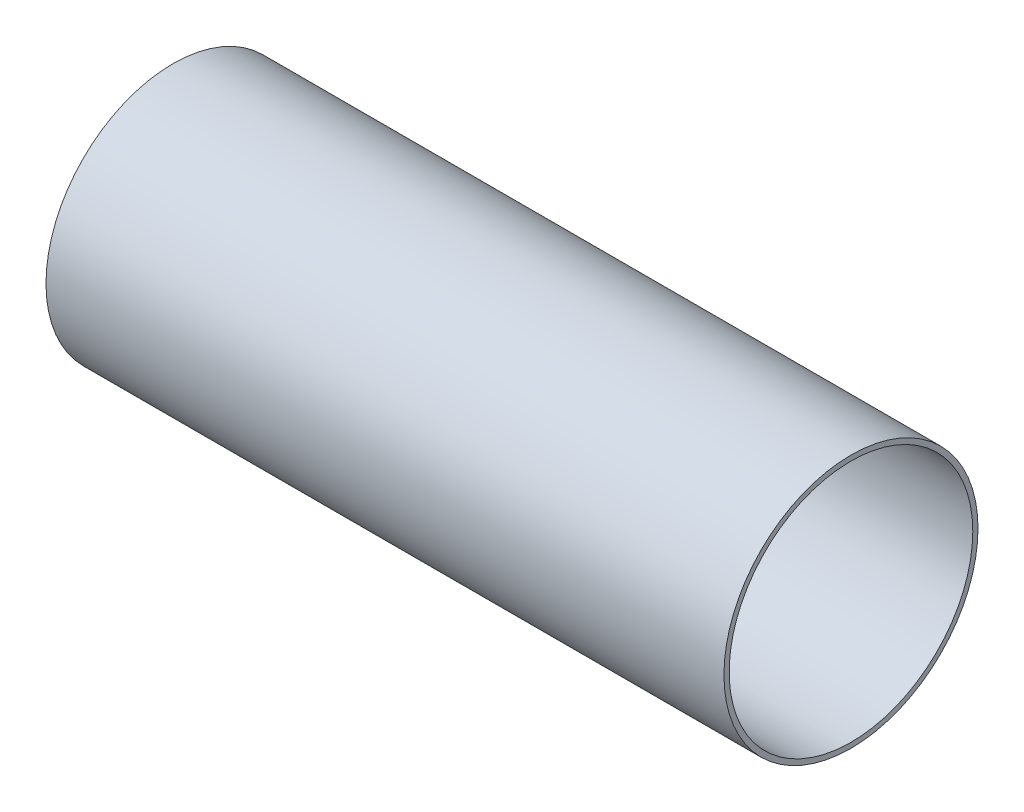
SolidWorks part; units mm, degrees
ref_plane "Front Plane" through (0, 0, 0) normal (1, 0, 0) x (0, 1, 0)
ref_plane "Top Plane" through (0, 0, 0) normal (0, 0, 1) x (0, 1, 0)
ref_plane "Right Plane" through (0, 0, 0) normal (0, 1, 0) x (-1, 0, 0)
sketch "Sketch1" plane through (0, 0, 0) normal (1, 0, 0) x (0, 1, 0)
  circle A0 centre (0, 0) radius 38.0746
  circle A1 centre (0, 0) radius 36.5125
  dimension "D1" = 76.1492
  dimension "D2" = 73.025
extrude "Boss-Extrude1" add sketch "Sketch1" along normal blind 203.2
